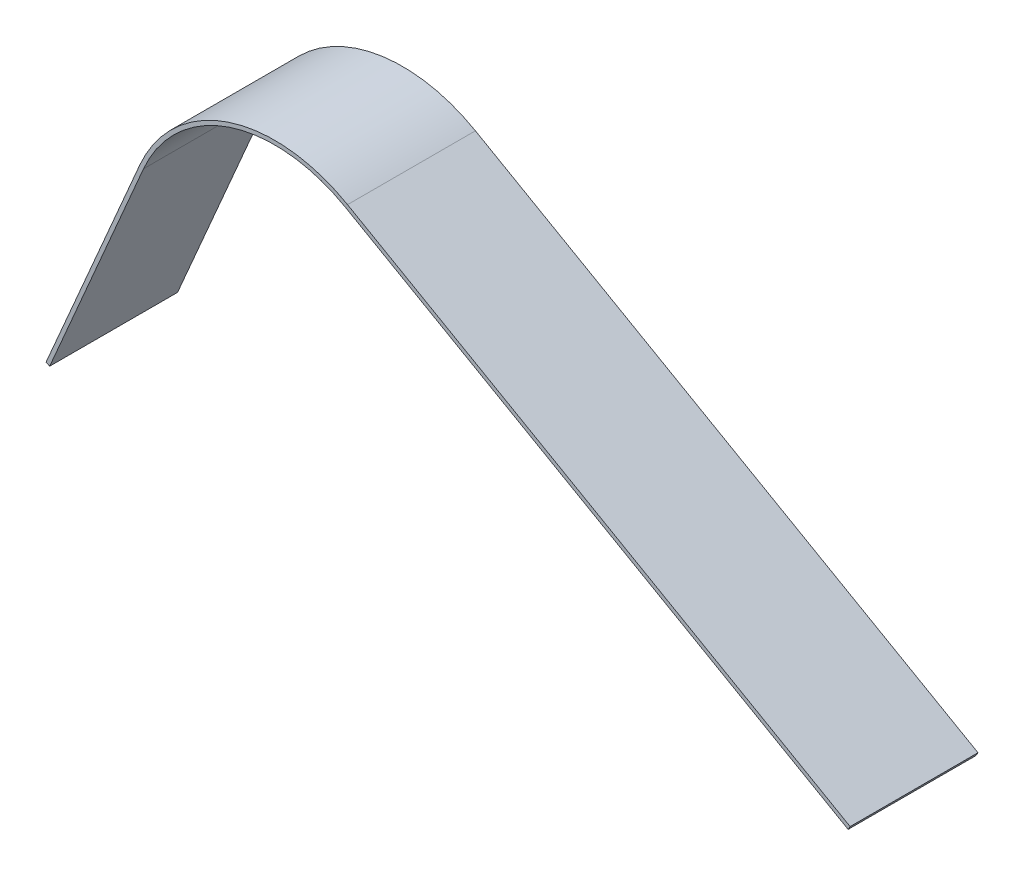
SolidWorks part; units mm, degrees
ref_plane "Front Plane" through (0, 0, 0) normal (0, 0, 1) x (1, 0, 0)
ref_plane "Top Plane" through (0, 0, 0) normal (0, 1, 0) x (1, 0, 0)
ref_plane "Right Plane" through (0, 0, 0) normal (1, 0, 0) x (0, 0, -1)
sketch "Sketch1" plane through (0, 0, 0) normal (0, 0, 1) x (1, 0, 0)
  line L0 (0, 0) -> (-457.2, 0) construction
  line L1 (-457.2, 0) -> (-457.2, 127) construction
  line L2 (-399.3165, 228.2607) -> (0, 0)
  line L3 (-457.2, 0) -> (-638.896, 0) construction
  line L4 (-638.896, 0) -> (-564.3234, 173.1391)
  line L5 (-638.896, 0) -> (-635.98, -1.256)
  line L6 (-564.3234, 173.1391) -> (-557.8763, 170.3623) construction
  line L7 (-635.98, -1.256) -> (-561.4073, 171.8831)
  line L8 (-399.3165, 228.2607) -> (-404.7884, 218.6883) construction
  line L9 (0, 0) -> (-0.0008, -0.0014)
  line L10 (-400.8921, 225.5043) -> (-1.5757, -2.7564)
  line L11 (-0.0008, -0.0014) -> (-1.5757, -2.7564)
  arc A0 (-564.3234, 173.1391) -> (-399.3165, 228.2607) centre (-457.2, 127) cw
  arc A1 (-561.4073, 171.8831) -> (-400.8921, 225.5043) centre (-457.2, 127) cw
  dimension "D2" = 127
  dimension "D3" = 3.175
extrude "Boss-Extrude1" add sketch "Sketch1" along normal blind 101.6
